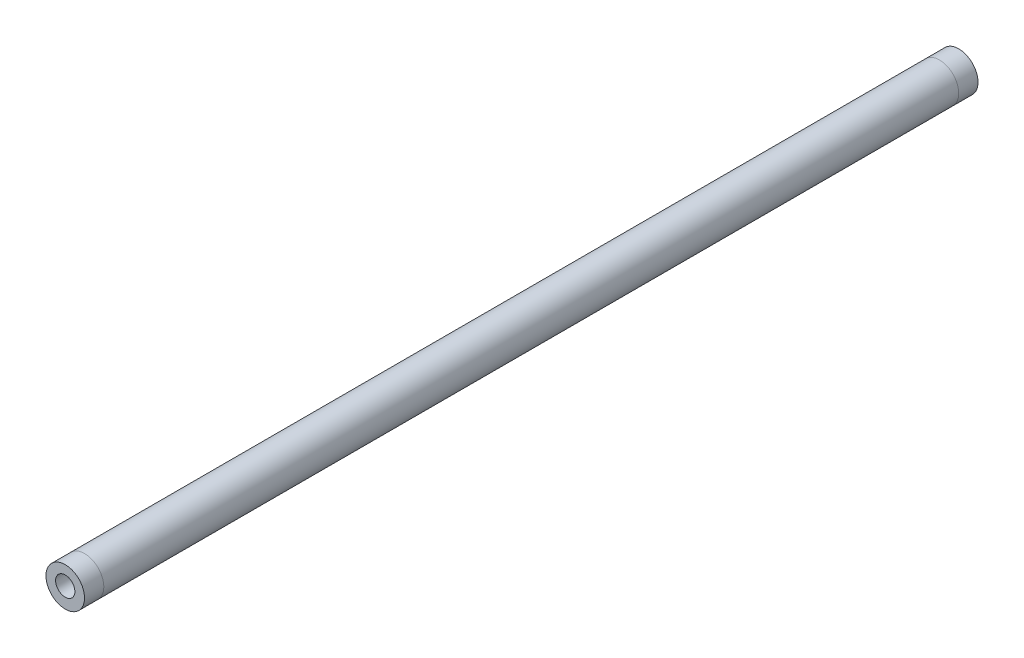
SolidWorks part; units mm, degrees
material "AISI 4130 Steel, normalized at 870C"
ref_plane "Front Plane" through (0, 0, 0) normal (0, 0, 1) x (1, 0, 0)
ref_plane "Top Plane" through (0, 0, 0) normal (0, 1, 0) x (1, 0, 0)
ref_plane "Right Plane" through (0, 0, 0) normal (1, 0, 0) x (0, 0, -1)
sketch "Axis" plane through (0, 0, 0) normal (0, 1, 0) x (1, 0, 0)
  line L0 (0, 0) -> (0, 21.8948) construction
  line L1 (0, 21.8948) -> (0, 316.1183) construction
  line L2 (0, 316.1183) -> (0, 338.0131) construction
  dimension "D1" = 21.8948
  dimension "D2" = 338.0131
sketch "Sketch2" plane through (0, 0, 0) normal (0, 0, 1) x (1, 0, 0)
  circle A0 centre (0, 0) radius 6.35
  circle A1 centre (0, 0.235) radius 3.175
  circle A2 centre (0, 0) radius 4.7625
  dimension "D1" = 12.7
  dimension "D2" = 6.35
  dimension "D3" = 9.525
extrude "Threaded Insert 1-1" add sketch "Sketch2" against normal blind 6.35 from vertex contours A0 A2 | A2 A1 region at (-6.1704, 0, 0) region at (-4.6278, 0, 0) starting at point (0, 0, -21.8948)
extrude "Threaded Insert 1-2" add sketch "Sketch2<5>" against normal blind 9.525 from surface contours A2 A1 region at (-4.6278, 0, 0) starting at face at (6.35, 0, -28.2448)
sketch "Sketch2<5>" plane through (0, 0, 0) normal (0, 0, 1) x (1, 0, 0) same geometry as "Sketch2"
extrude "Boss-Extrude4" add sketch "Sketch2<7>" along normal blind 6.35 from vertex separate body contours A0 A2 | A2 A1 region at (-6.1704, 0, 0) region at (-4.6278, 0, 0) starting at point (0, 0, -316.1183)
sketch "Sketch2<7>" plane through (0, 0, 0) normal (0, 0, 1) x (1, 0, 0) same geometry as "Sketch2"
extrude "Boss-Extrude5" add sketch "Sketch2<8>" along normal blind 9.525 from surface contours A2 A1 region at (-4.6278, 0, 0) starting at face at (6.35, 0, -309.7683)
sketch "Sketch2<8>" plane through (0, 0, 0) normal (0, 0, 1) x (1, 0, 0) same geometry as "Sketch2"
extrude "Boss-Extrude6" add sketch "Sketch2<9>" against normal up to surface (309.7683 mm away) from surface separate body contours A0 A2 region at (-6.1704, 0, 0) up to face at (6.35, 0, -309.7683) starting at face at (4.7625, 0, -28.2448)
sketch "Sketch2<9>" plane through (0, 0, 0) normal (0, 0, 1) x (1, 0, 0) same geometry as "Sketch2"
equation "\"Tube Outer Diameter\"= .5"
equation "\"Tube Inner Diameter\"= .375"
equation "\"Rod end Diameter\"= .25"
equation "\"Threaded Insert Out\"= .25"
equation "\"Threaded Insert In\"= .375'`"
equation "\"D1@Sketch2\"=\"Tube Outer Diameter\""
equation "\"D2@Sketch2\"=\"Rod end Diameter\""
equation "\"D1@Threaded Insert 1-1\" = \"Threaded Insert Out\""
equation "\"D3@Sketch2\"=\"Tube Inner Diameter\""
equation "\"D1@Threaded Insert 1-2\" = \"Threaded Insert In\""
equation "\"D1@Boss-Extrude4\"=\"Threaded Insert Out\""
equation "\"D1@Boss-Extrude5\"=\"Threaded Insert In\""
